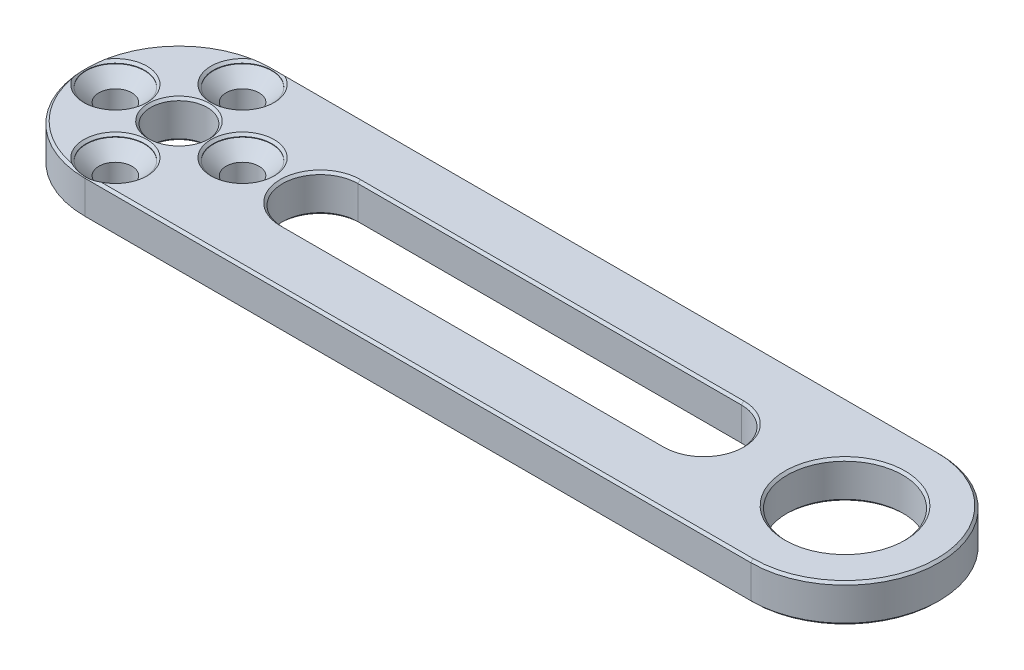
SolidWorks part; units mm, degrees
ref_plane "Front Plane" through (0, 0, 0) normal (0, 0, 1) x (1, 0, 0)
ref_plane "Top Plane" through (0, 0, 0) normal (0, 1, 0) x (1, 0, 0)
ref_plane "Right Plane" through (0, 0, 0) normal (1, 0, 0) x (0, 0, -1)
sketch "Sketch1" plane through (0, 0, 0) normal (0, 1, 0) x (1, 0, 0)
  line L0 (0, 0) -> (70.71, 0) construction
  line L1 (0, 10) -> (70.71, 10)
  line L2 (0, -10) -> (70.71, -10)
  line L3 (0, 18.6761) -> (0, -19.8554) construction
  line L4 (15, 0) -> (55.71, 0) construction
  line L5 (15, 4) -> (55.71, 4)
  line L6 (15, -4) -> (55.71, -4)
  arc A0 (0, 10) -> (0, -10) centre (0, 0) ccw
  arc A1 (70.71, -10) -> (70.71, 10) centre (70.71, 0) ccw
  circle A2 centre (0, 0) radius 6.75 construction
  circle A3 centre (0, 6.75) radius 1.75
  circle A4 centre (6.75, 0) radius 1.75
  circle A5 centre (0, -6.75) radius 1.75
  circle A6 centre (-6.75, 0) radius 1.75
  circle A7 centre (0, 0) radius 3
  circle A8 centre (70.71, 0) radius 6.125
  arc A9 (15, 4) -> (15, -4) centre (15, 0) ccw
  arc A10 (55.71, -4) -> (55.71, 4) centre (55.71, 0) ccw
  point P3 (35.355, 0)
  point P25 (35.355, 0)
  dimension "D1" = 10
  dimension "D3" = 13.5
  dimension "D4" = 3.5
  dimension "D5" = 6
  dimension "D6" = 12.25
  dimension "D8" = 4
  dimension "D2" = 70.71
  dimension "D7" = 15
extrude "Boss-Extrude1" add sketch "Sketch1" along normal mid plane 4
hole_wizard "CSK for M3 Flat Head Machine Screw2" positions "Sketch2" profile "Sketch3" countersink size "M3" standard "ANSI Metric" end condition through all
sketch "Sketch2" plane through (0, 2, 0) normal (0, 1, 0) x (1, 0, 0)
  point P0 (0, 6.75)
  point P3 (6.75, 0)
  point P6 (0, -6.75)
  point P9 (-6.75, 0)
sketch "Sketch3" plane through (0, 2, -6.75) normal (1, 0, 0) x (0, 0, 1)
  line L0 (0, 0) -> (0, 4)
  line L1 (0, 4) -> (1.75, 4)
  line L2 (1.75, 4) -> (1.75, 1.65)
  line L3 (1.75, 1.65) -> (3.1, 0.3)
  line L4 (3.1, 0.3) -> (3.1, 0)
  line L6 (3.1, 0) -> (0, 0)
  line L7 (-1.75, 1.65) -> (-3.1, 0.3) construction
  line L11 (0, -6.35) -> (0, 107.95) construction
  dimension "Thru Hole Dia." = 3.5
  dimension "Thru Hole Depth" = 4
  dimension "C'Sink Dia." = 6.2
  dimension "C'Sink Angle" = 90
  dimension "Head Clearance" = 0.3
chamfer "Chamfer1" distance 0.25 angle 45 28 edges at (35.355, -2, -4) (59.71, -2, 0) (35.355, -2, 4) (11, -2, 0) (35.355, -2, 10) (80.71, -2, 0) (35.355, -2, -10) (-10, -2, 0) (0, -2, -5) (6.75, -2, 1.75) (0, -2, 8.5) (-6.75, -2, 1.75) (0, -2, 3) (70.71, -2, 6.125) (59.71, 2, 0) (35.355, 2, -4) (11, 2, 0) (35.355, 2, 4) (70.71, 2, 6.125) (35.355, 2, -10) (80.71, 2, 0) (35.355, 2, 10) (-10, 2, 0) (0, 2, 3) (-6.75, 2, 3.1) (0, 2, 9.85) (6.75, 2, 3.1) (0, 2, -3.65)
